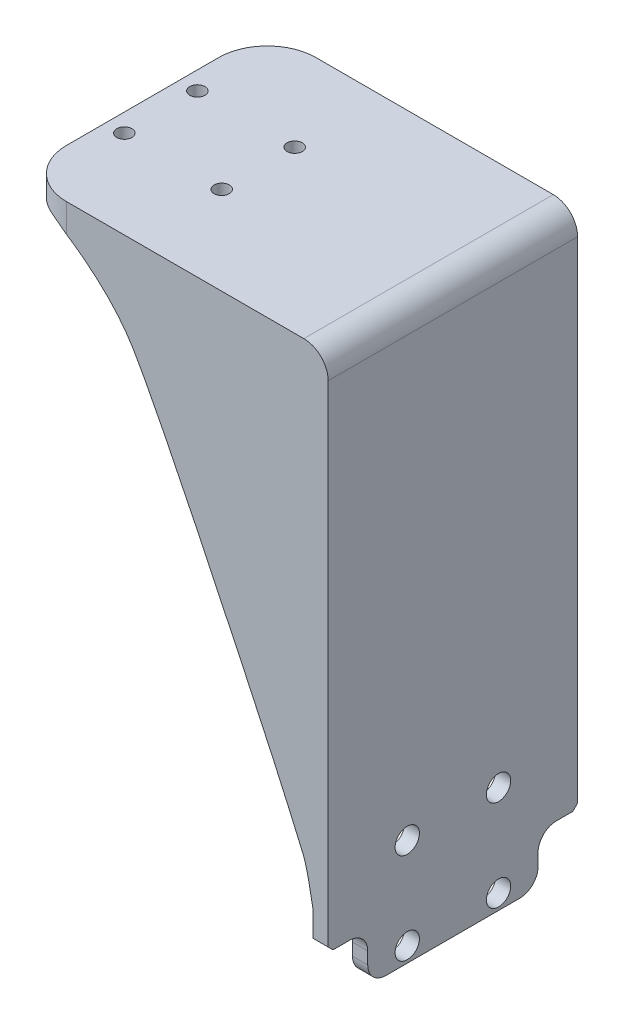
SolidWorks part; units mm, degrees
ref_plane "前视基准面" through (0, 0, 0) normal (0, 0, 1) x (1, 0, 0)
ref_plane "上视基准面" through (0, 0, 0) normal (0, 1, 0) x (1, 0, 0)
ref_plane "右视基准面" through (0, 0, 0) normal (1, 0, 0) x (0, 0, -1)
other "Configuration Table"
sketch "草图1" plane through (0, 0, 0) normal (0, 1, 0) x (1, 0, 0)
  line L0 (-22.5, 11.2328) -> (-22.5, -19.6928) construction
  line L1 (-25.5, 20.5) -> (25.5, 20.5)
  line L2 (-25.5, 20.5) -> (-25.5, -20.5)
  line L3 (-25.5, -20.5) -> (25.5, -20.5)
  line L4 (25.5, 20.5) -> (25.5, -20.5)
  line L5 (-25.5, 20.5) -> (25.5, -20.5) construction
  line L6 (-25.5, -20.5) -> (25.5, 20.5) construction
  line L7 (-17.7344, 0) -> (22.5332, 0) construction
  circle A0 centre (-22.5, 6) radius 1.25
  circle A1 centre (-22.5, -6) radius 1.25
  circle A2 centre (-6.5, 6) radius 1.25
  circle A3 centre (-6.5, -6) radius 1.25
  point P0 (0, 0)
  dimension "D3" = 2.5
  dimension "D4" = 12
  dimension "D6" = 16
  dimension "D7" = 2.5
  dimension "D1" = 41
  dimension "D2" = 3
  dimension "D5" = 51
extrude "凸台-拉伸1" add sketch "草图1" along normal blind 3.4
sketch "草图2" plane through (25.5, 0, 0) normal (1, 0, 0) x (0, 0, -1)
  line L0 (-20.5, 0) -> (20.5, 0)
  line L1 (20.5, 0) -> (20.5, -90)
  line L2 (20.5, -90) -> (10.6377, -90)
  line L3 (-20.5, -90) -> (-20.5, 0)
  line L4 (0, 12.0877) -> (0, -113.9375) construction
  line L5 (-30.0581, -80) -> (27.3842, -80) construction
  line L6 (10.6377, -90) -> (-20.5, -90)
  line L7 (0, -64) -> (0, -84.8169) construction
  circle A0 centre (-7.5, -87.5) radius 1
  circle A1 centre (7.5, -87.5) radius 1
  circle A2 centre (7.5, -72.5) radius 1
  circle A3 centre (-7.5, -72.5) radius 1
  dimension "D3" = 2
  dimension "D4" = 15
  dimension "D5" = 15
  dimension "D1" = 90
  dimension "D2" = 10
extrude "凸台-拉伸2" add sketch "草图2" against normal blind 2.5
sketch "草图5" plane through (0, 0, -20.5) normal (0, 0, -1) x (-1, 0, 0)
  line L0 (-25.5, 3.4) -> (19.5, 3.4)
  line L1 (-25.5, -77) -> (-25.5, 3.4)
  line L2 (19.5, 3.4) -> (19.5, 0)
  line L3 (-25.5, -77) -> (-23, -77)
  line L4 (-23, -90) -> (-25.5, -90) construction
  line L5 (-25.5, 3.4) -> (-25.5, -90) construction
  line L6 (25.5, 3.4) -> (25.5, 0) construction
  line L7 (-23, -90) -> (-23, 0) construction
  spline S0 degree 2 poles (19.5, 0) (10.6712, -5.3693) (2.7794, -18.1934) (-17.7405, -61.46) (-22.1031, -71.7396) (-23, -77) knots 0 0 0 0.396049 0.78858 0.966138 1 1 1
  point P7 (-25.5, 3.4)
  dimension "D1" = 6
  dimension "D2" = 13
extrude "凸台-拉伸4" add sketch "草图5" against normal blind 2
sketch "草图11" plane through (25.5, 0, 0) normal (1, 0, 0) x (0, 0, -1)
  line L0 (0, 21.7008) -> (0, -153.0759) construction
  line L1 (-12, -68) -> (12, -68)
  line L2 (12, -68) -> (12, -90)
  line L3 (-20.5, -90) -> (20.5, -90) construction
  line L4 (12, -90) -> (-12, -90)
  line L5 (-12, -68) -> (-12, -90)
  circle A0 centre (7.5, -87.5) radius 1 construction
  circle A1 centre (7.5, -72.5) radius 1 construction
  circle A2 centre (-7.5, -87.5) radius 1 construction
  circle A3 centre (-7.5, -72.5) radius 1 construction
  circle A4 centre (7.5, -87.5) radius 1
  circle A5 centre (7.5, -72.5) radius 1
  circle A6 centre (-7.5, -87.5) radius 1
  circle A7 centre (-7.5, -72.5) radius 1
  point P10 (0, -90)
  point P11 (0, -68)
  dimension "D1" = 22
  dimension "D2" = 12
mirror "镜向3" about plane through (0, 0, 0) normal (0, 0, 1) of "凸台-拉伸4"
fillet "圆角1" radius 8 2 edges at (-25.5, 1.7, -20.5) (-25.5, 1.7, 20.5)
fillet "圆角2" radius 4 2 edges at (23, 0, 0) (25.5, 3.4, 0)
sketch "草图6" plane through (23, 0, 0) normal (-1, 0, 0) x (0, 0, 1)
  circle A0 centre (7.5, -87.5) radius 2
  circle A1 centre (-7.5, -87.5) radius 2
  dimension "D1" = 4
  dimension "D2" = 4
extrude "切除-拉伸2" cut sketch "草图6" against normal blind 4
sketch "草图8" plane through (25.5, 0, 0) normal (1, 0, 0) x (0, 0, -1)
  line L0 (14, -102.818) -> (14, -82)
  line L1 (14, -82) -> (23.4685, -82)
  line L2 (23.4685, -82) -> (23.4685, -110.0082)
  line L3 (23.4685, -110.0082) -> (-23.4685, -110.0082)
  line L4 (-23.4685, -82) -> (-23.4685, -110.0082)
  line L5 (0, -27.3846) -> (0, -80.1854) construction
  line L6 (-14, -82) -> (-23.4685, -82)
  line L7 (-14, -102.818) -> (-14, -82)
  line L8 (-14, -102.818) -> (14, -102.818)
  line L9 (-20.5, -90) -> (20.5, -90) construction
  point P9 (0, -110.0082)
  dimension "D1" = 28
  dimension "D2" = 8
extrude "切除-拉伸3" cut sketch "草图8" against normal blind 4
fillet "圆角3" radius 3 4 edges at (24.25, -90, -14) (24.25, -82, -14) (24.25, -82, 14) (24.25, -90, 14)
sketch "草图9" plane through (23, 0, 0) normal (-1, 0, 0) x (0, 0, 1)
  line L0 (0, 14.9311) -> (0, -25.9548) construction
  circle A0 centre (7.5, -72.5) radius 2
  circle A1 centre (-7.5, -72.5) radius 2
  dimension "D1" = 4
extrude "切除-拉伸4" cut sketch "草图9" against normal blind 4
sketch "草图10" plane through (0, 0, 0) normal (0, -1, 0) x (-1, 0, 0)
  line L0 (28.9726, 0) -> (-5.0372, 0) construction
  line L1 (6.5, -6) -> (22.5, -6) construction
  line L2 (14.5, -8.9106) -> (14.5, 10.615) construction
  circle A0 centre (6.5, -6) radius 2.5
  circle A2 centre (22.5, -6) radius 2.5
  circle A3 centre (6.5, 6) radius 2.5
  circle A4 centre (22.5, 6) radius 2.5
  dimension "D1" = 5
extrude "切除-拉伸5" cut sketch "草图10" against normal blind 1.4
chamfer "倒角1" distance 0.8 angle 45 2 edges at (24.25, -82, 20.5) (24.25, -82, -20.5)
fillet "圆角4" radius 4 6 edges at (-0.25, 0, -18.5) (21.8284, -1.1716, -18.5) (-0.25, 0, 18.5) (21.8284, -1.1716, 18.5) (23, -40.5, -18.5) (23, -40.5, 18.5)
fillet "圆角5" radius 5 2 edges at (-19.5, 0, 17.373) (-19.5, 0, -17.373)
